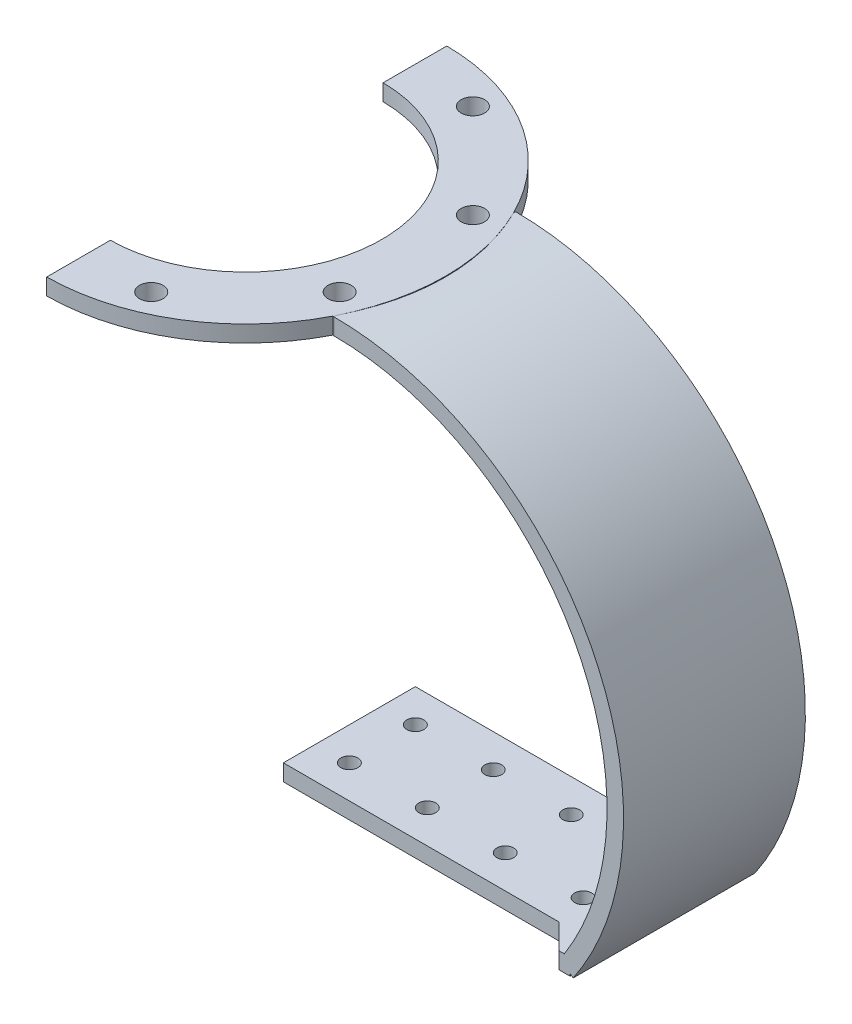
SolidWorks part; units mm, degrees
other "DetailItem1"
other "DetailItem2"
other "DetailItem3"
material "Copper"
ref_plane "Front Plane" through (0, 0, 0) normal (0, 0, 1) x (1, 0, 0)
ref_plane "Top Plane" through (0, 0, 0) normal (0, 1, 0) x (1, 0, 0)
ref_plane "Right Plane" through (0, 0, 0) normal (1, 0, 0) x (0, 0, -1)
ref_plane "40K Bottom Cold head Location" through (0, 87.18, 0) normal (0, 1, 0) x (1, 0, 0)
sketch "Sketch1" plane through (0, 0, 0) normal (0, 1, 0) x (1, 0, 0)
  line L0 (77.84, 17.5) -> (77.84, -17.5)
  line L5 (20, 12.7) -> (80, 12.7)
  line L6 (20, 12.7) -> (20, -12.7)
  line L7 (20, -12.7) -> (80, -12.7)
  line L8 (80, 12.7) -> (80, -12.7)
  line L9 (77.84, 17.5) -> (80, 17.5)
  line L10 (80, 17.5) -> (80, 12.7)
  line L11 (77.84, -17.5) -> (80, -17.5)
  line L12 (80, -17.5) -> (80, -12.7)
  circle A0 centre (26.35, 6.35) radius 1.63
  circle A1 centre (41.35, 6.35) radius 1.63
  circle A2 centre (56.35, 6.35) radius 1.63
  circle A3 centre (41.35, -6.35) radius 1.63
  circle A4 centre (56.35, -6.35) radius 1.63
  circle A5 centre (26.35, -6.35) radius 1.63
  circle A6 centre (71.35, 6.35) radius 1.63
  circle A7 centre (71.35, -6.35) radius 1.63
  point P11 (77.84, 0)
  point P12 (80, 0)
  dimension "D5" = 3.26
  dimension "D1" = 60
  dimension "D2" = 25.4
  dimension "D3" = 6.35
  dimension "D4" = 6.35
  dimension "D6" = 15
  dimension "D7" = 12.7
  dimension "D10" = 20
  dimension "D11" = 12.7
  dimension "D12" = 35
  dimension "D13" = 2.16
  dimension "D14" = 15
sketch "Sketch2" plane through (0, 87.18, 0) normal (0, 1, 0) x (1, 0, 0)
  line L0 (0, 26) -> (0, -26) construction
  line L1 (0, 0) -> (12.8199, 30.95) construction
  line L2 (0.25, 38.4992) -> (0.25, 26.2488)
  line L3 (0.25, -38.4992) -> (0.25, -26.2488)
  circle A0 centre (0, 0) radius 26
  circle A1 centre (12.8199, 30.95) radius 2.25
  circle A2 centre (30.95, 12.8199) radius 2.25
  circle A3 centre (30.95, -12.8199) radius 2.25
  circle A4 centre (12.8199, -30.95) radius 2.25
  circle A5 centre (-12.8199, -30.95) radius 2.25 [skipped]
  circle A6 centre (-30.95, -12.8199) radius 2.25 [skipped]
  circle A7 centre (-30.95, 12.8199) radius 2.25 [skipped]
  circle A8 centre (-12.8199, 30.95) radius 2.25 [skipped]
  circle A9 centre (0, 0) radius 38.5
  circle A10 centre (0, 0) radius 26.25
  point P25 (0, 0)
  dimension "D1" = 52
  dimension "D3" = 4.5
  dimension "D8" = 77
  dimension "D9" = 52.5
  dimension "D2" = 33.5
  dimension "D4" = 22.5
  dimension "D6" = 33.5
  dimension "D7" = 33.5
  dimension "D10" = 0.25
  dimension "D5" = 8
ref_plane "Top_Connection_Plane" through (34.5, 0, 0) normal (1, 0, 0) x (0, 0, -1)
ref_plane "Bottom_Connection_Plane" through (80.58, 0, 0) normal (1, 0, 0) x (0, 0, -1)
extrude "Boss-Extrude1" add sketch "Sketch2" against normal blind 3.175 contours A10 L3 A9 L2 A1 A2 A3 A4 region at (26.7019, 87.18, -26.5291)
extrude "Boss-Extrude2" add sketch "Sketch1" along normal blind 3.175 separate body contours L6 L7 L0 L5 A5 A4 A3 A2 A1 A0 | L11 L12 L7 L0 | L8 L5 L0 L7 | L10 L9 L0 L5 region at (78.92, 0, -15.1) region at (78.92, 0, 0) region at (48.9233, 0, 0) region at (78.92, 0, 15.1)
sketch "Top_Connection_Sketch" plane through (34.5, 0, 0) normal (1, 0, 0) x (0, 0, -1)
  line L0 (69.5032, 87.18) -> (-69.5032, 87.18) construction
  line L1 (-17.5, 87.18) -> (17.5, 87.18)
  line L2 (-17.5, 87.18) -> (-17.5, 84.005)
  line L3 (-17.5, 84.005) -> (17.5, 84.005)
  line L4 (17.5, 87.18) -> (17.5, 84.005)
  line L5 (-38.4992, 84.005) -> (38.4992, 84.005) construction
  point P6 (0, 84.005)
  dimension "D1" = 35
sketch "Sketch5" plane through (80.58, 0, 0) normal (1, 0, 0) x (0, 0, -1)
  line L1 (-17.5, 3.175) -> (17.5, 3.175)
  line L2 (-17.5, 3.175) -> (-17.5, 0)
  line L3 (-17.5, 0) -> (17.5, 0)
  line L4 (17.5, 3.175) -> (17.5, 0)
  line L5 (17.5, 3.175) -> (-17.5, 3.175) construction
  dimension "D1" = 35
sketch3d "3DSketch2"
  arc A0 (80.58, 0, 17.5) -> (34.5, 87.18, 17.5) centre (34.5, 31.4119, 17.5) ccw
  point P2 (34.5, 31.4119, 73.2681)
  point P10 (34.5, 87.18, 17.5)
  point P13 (80.58, 0, 17.5)
sweep "Sweep2" add profiles "Top_Connection_Sketch" path "3DSketch2"
chamfer "Chamfer1" distance 4.8 angle 45 2 edges at (77.84, 1.5875, -12.7) (77.84, 1.5875, 12.7)
chamfer "Chamfer2" distance 0.41 angle 84 1 edges at (34.5, 85.5925, 17.088) first distance on face at (34.5, 85.5925, 17.294)
equation "\"D4@Sketch1\"=\"D3@Sketch1\""
equation "\"D7@Sketch2\"=\"D2@Sketch2\""
equation "\"D6@Sketch2\"=\"D2@Sketch2\""
equation "\"Distance_From_Cold_Center\"=20"
equation "\"D10@Sketch1\"=\"Distance_From_Cold_Center\""
equation "\"D11@Sketch1\"=\"D2@Sketch1\"/2"
equation "\"Inside_Cold_Rod_Dia\"=52"
equation "\"D1@Sketch2\"=\"Inside_Cold_Rod_Dia\""
equation "\"40K_Cold_Head_Dia\"=77"
equation "\"D8@Sketch2\"=\"40K_Cold_Head_Dia\""
equation "\"D14@Sketch1\"=\"D6@Sketch1\""
